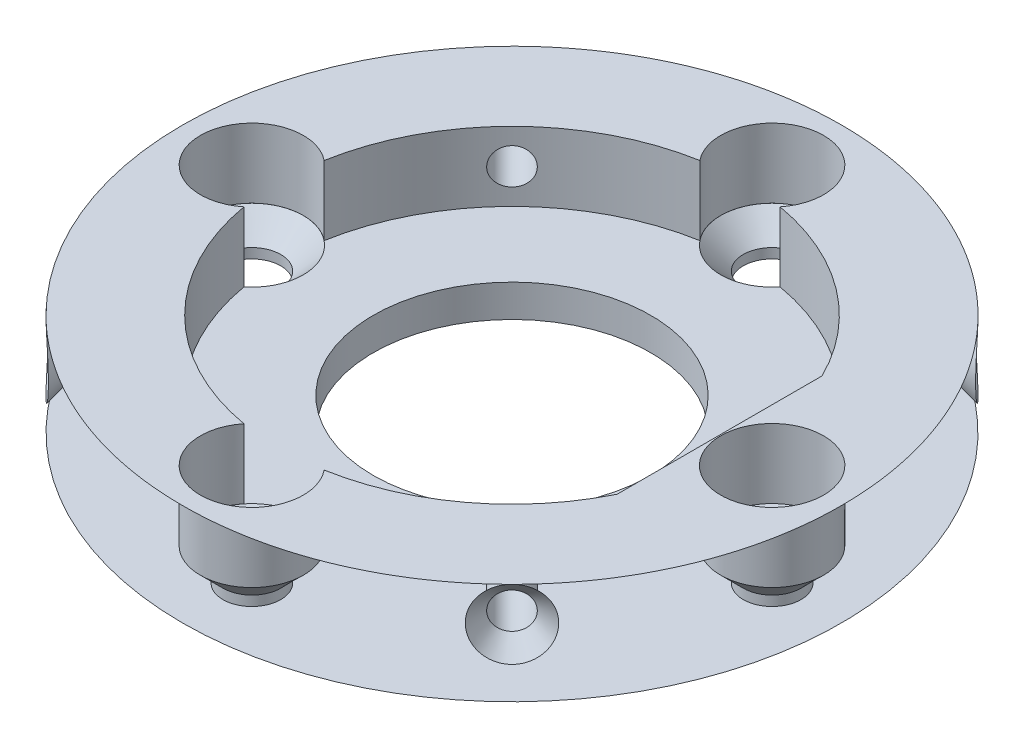
SolidWorks part; units mm, degrees
ref_plane "Front Plane" through (0, 0, 0) normal (0, 0, 1) x (1, 0, 0)
ref_plane "Top Plane" through (0, 0, 0) normal (0, 1, 0) x (1, 0, 0)
ref_plane "Right Plane" through (0, 0, 0) normal (1, 0, 0) x (0, 0, -1)
sketch "草图1" plane through (0, 0, 0) normal (0, 1, 0) x (1, 0, 0)
  circle A0 centre (0, 0) radius 28.5
  dimension "D1" = 57
extrude "凸台-拉伸1" add sketch "草图1" along normal blind 8.8
sketch "草图2" plane through (0, 8.8, 0) normal (0, 1, 0) x (1, 0, 0)
  circle A0 centre (-22.5, 0) radius 4.45
  dimension "D1" = 8.9
  dimension "D2" = 22.5
extrude "切除-拉伸1" cut sketch "草图2" against normal blind 6
hole_wizard "CSK for #0 Flat Head Machine Screw (100)4" positions "草图10" profile "草图11" countersink size "#0" standard "ANSI Inch" end condition through all
sketch "草图10" plane through (0, 2.8, 0) normal (0, 1, 0) x (1, 0, 0)
  point P0 (-22.5, 0)
sketch "草图11" plane through (-22.5, 2.8, 0) normal (1, 0, 0) x (0, 0, 1)
  line L0 (0, 0) -> (0, 2.8)
  line L1 (0, 2.8) -> (2.5, 2.8)
  line L2 (2.5, 2.8) -> (2.5, 1.945)
  line L3 (2.5, 1.945) -> (4.445, 0)
  line L5 (4.445, 0) -> (0, 0)
  line L6 (-2.5, 1.945) -> (-4.445, 0) construction
  line L11 (0, -6.35) -> (0, 107.95) construction
  dimension "Thru Hole Dia." = 5
  dimension "Thru Hole Depth" = 2.8
  dimension "Near C'Sink Dia." = 8.89
  dimension "Near C'Sink Angle" = 90
ref_axis "基准轴1" through (0, 8.8, 0) along (0, -1, 0)
sketch "草图14" plane through (0, 8.8, 0) normal (0, 1, 0) x (1, 0, 0)
  circle A0 centre (0, 0) radius 20.02
  dimension "D1" = 40.04
extrude "切除-拉伸5" cut sketch "草图14" against normal blind 6
ref_plane "基准面2" through (0, 5.8, 0) normal (0, 1, 0) x (1, 0, 0)
sketch "草图16" plane through (0, 5.8, 0) normal (0, 1, 0) x (1, 0, 0)
  line L0 (0, 0) -> (-22.5, 0) construction
  line L1 (0, 0) -> (-20.1525, 20.1525) construction
  line L6 (17.95, 8.8655) -> (17.95, -8.8655)
  line L7 (17.95, 8.8655) -> (20.02, 8.8655)
  line L8 (20.02, 8.8655) -> (20.02, -8.8655)
  line L9 (20.02, -8.8655) -> (17.95, -8.8655)
  circle A0 centre (0, 0) radius 28.5 construction
  arc A3 (-19.7166, -3.4721) -> (-19.7166, 3.4721) centre (0, 0) ccw construction
  arc A4 (-19.7166, -3.4721) -> (-19.7166, 3.4721) centre (0, 0) ccw construction
  dimension "D1" = 45
  dimension "D2" = 17.95
extrude "凸台-拉伸2" add sketch "草图16" along normal blind 3 and the other way blind 3
hole_wizard "CSK for #0 Flat Head Machine Screw (100)5" positions "3D草图2" profile "草图19" countersink size "#0" standard "ANSI Inch"
sketch3d "3D草图2"
  point P0 (-20.1525, 5.8, -20.1525)
sketch "草图19" plane through (-20.1525, 5.8, -20.1525) normal (0, 1, 0) x (-0.7071, 0, 0.7071)
  line L0 (0, 0) -> (0, 20.9313)
  line L1 (0, 20.9313) -> (1.55, 20)
  line L2 (1.55, 20) -> (1.55, 1.45)
  line L3 (1.55, 1.45) -> (3, 0)
  line L5 (3, 0) -> (0, 0)
  line L6 (-1.55, 1.45) -> (-3, 0) construction
  line L10 (0, 20.9313) -> (-1.55, 20) construction
  line L11 (0, -6.35) -> (0, 107.95) construction
  dimension "Hole Dia." = 3.1
  dimension "Hole Depth" = 20
  dimension "Near C'Sink Dia." = 6
  dimension "Near C'Sink Angle" = 90
  dimension "Drill Angle" = 118
pattern_circular "阵列(圆周)7" count 4 every 90 about axis through (0, 8.8, 0) along (0, -1, 0) of "CSK for #0 Flat Head Machine Screw (100)5", "CSK for #0 Flat Head Machine Screw (100)4", "切除-拉伸1"
sketch "草图21" plane through (0, 2.8, 0) normal (0, 1, 0) x (1, 0, 0)
  circle A0 centre (0, 0) radius 12
extrude "切除-拉伸6" cut sketch "草图21" against normal through all
